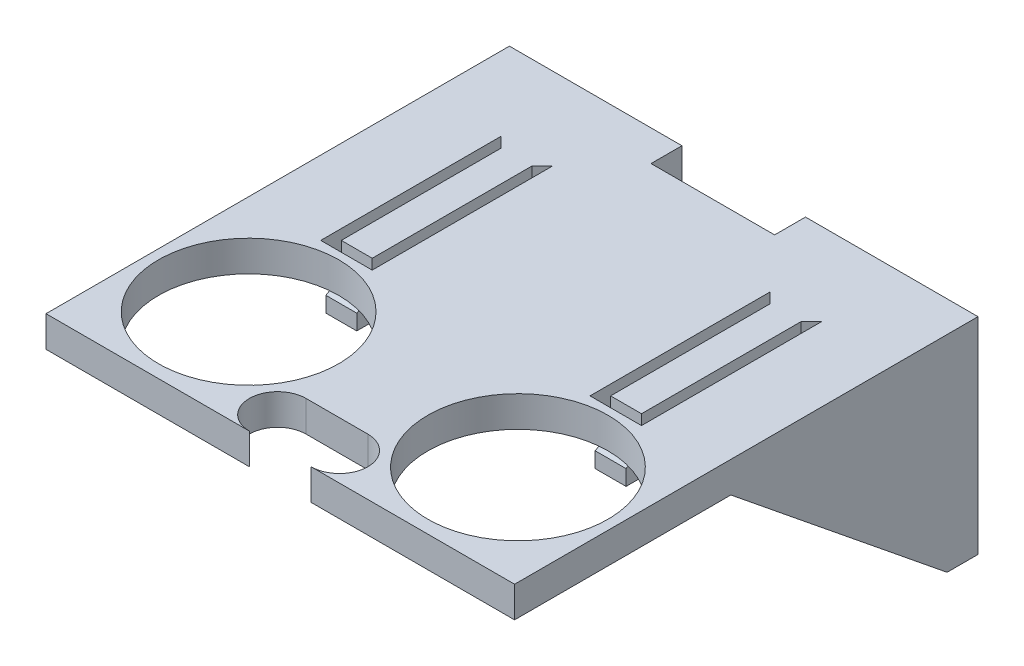
SolidWorks part; units mm, degrees
ref_plane "Front" through (0, 0, 0) normal (0, 0, 1) x (1, 0, 0)
ref_plane "Top" through (0, 0, 0) normal (0, 1, 0) x (1, 0, 0)
ref_plane "Right" through (0, 0, 0) normal (1, 0, 0) x (0, 0, -1)
sketch "Sketch1" plane through (0, 0, 0) normal (0, 0, 1) x (1, 0, 0)
  line L0 (-19.8496, -3.9653) -> (-19.8496, 16.0347)
  line L1 (-36.5996, 16.0347) -> (8.9004, 16.0347)
  line L2 (-36.5996, 16.0347) -> (-36.5996, -3.9653)
  line L3 (-36.5996, -3.9653) -> (8.9004, -3.9653)
  line L4 (8.9004, 16.0347) -> (8.9004, -3.9653)
  line L5 (-7.8496, -3.9653) -> (-7.8496, 16.0347)
  point P12 (-13.8496, 16.0347)
  dimension "D1" = 45.5
  dimension "D2" = 20
  dimension "D9" = 6
  dimension "D10" = 6
extrude "Boss-Extrude1" add sketch "Sketch1" along normal blind 3 contours L2 L3 L0 L1 | L5 L3 L4 L1 region at (-28.2246, 6.0347, 0) region at (0.5254, 6.0347, 0)
sketch "Sketch2" plane through (0, 0, 3) normal (0, 0, 1) x (1, 0, 0)
  line L1 (-36.5996, 16.0347) -> (8.9004, 16.0347)
  line L2 (-36.5996, 16.0347) -> (-36.5996, 13.0347)
  line L3 (-36.5996, 13.0347) -> (8.9004, 13.0347)
  line L4 (8.9004, 16.0347) -> (8.9004, 13.0347)
  line L5 (8.9004, 16.0347) -> (8.9004, -3.9653) construction
  dimension "D1" = 3
extrude "Boss-Extrude2" add sketch "Sketch2" along normal blind 42 contours L3 L4 L1 L2
sketch "Sketch3" plane through (0, 13.0347, 0) normal (0, -1, 0) x (-1, 0, 0)
  line L0 (36.5996, -45) -> (-8.9004, -45) construction
  line L1 (18.1746, -35) -> (9.5246, -35)
  circle A0 centre (26.9246, -35) radius 8.75
  circle A1 centre (0.7746, -35) radius 8.75
  point P8 (13.8496, -35)
  point P9 (13.8496, -45)
  dimension "D1" = 17.5
  dimension "D2" = 17.5
  dimension "D3" = 10
  dimension "D4" = 10
  dimension "D5" = 26.15
extrude "Cut-Extrude1" cut sketch "Sketch3" against normal through all contours A0 | A1 region at (-0.7746, 13.0347, 35) region at (-26.9246, 13.0347, 35)
sketch "Sketch4" plane through (8.9004, 0, 0) normal (1, 0, 0) x (0, 0, -1)
  line L0 (-3, -3.9653) -> (-24, 13.0347)
  line L1 (-45, 13.0347) -> (-3, 13.0347) construction
  line L2 (-24, 13.0347) -> (-3, 13.0347)
  line L3 (-3, 16.0347) -> (-3, -3.9653) construction
  line L4 (-3, 13.0347) -> (-3, -3.9653)
  dimension "D1" = 21
extrude "Boss-Extrude3" add sketch "Sketch4" against normal blind 2
pattern_linear "LPattern1" count 2 spacing 43.5 along (-1, 0, 0) of "Boss-Extrude3"
sketch "Sketch5" plane through (0, 13.0347, 0) normal (0, -1, 0) x (-1, 0, 0)
  line L0 (29.4246, -8) -> (29.4246, -25.5)
  line L1 (29.4246, -25.5) -> (24.4246, -25.5)
  line L2 (24.4246, -25.5) -> (24.4246, -8)
  line L3 (24.4246, -8) -> (25.4246, -8)
  line L4 (25.4246, -8) -> (25.4246, -24.5)
  line L5 (25.4246, -24.5) -> (28.4246, -24.5)
  line L6 (28.4246, -24.5) -> (28.4246, -8)
  line L7 (28.4246, -8) -> (29.4246, -8)
  line L8 (36.5996, -45) -> (-8.9004, -45) construction
  line L9 (34.5996, -3) -> (19.8496, -3) construction
  line L11 (13.8496, -45) -> (13.8496, -32.1492)
  line L12 (-0.7254, -8) -> (-1.7254, -8)
  line L13 (-0.7254, -24.5) -> (-0.7254, -8)
  line L14 (2.2746, -24.5) -> (-0.7254, -24.5)
  line L15 (2.2746, -8) -> (2.2746, -24.5)
  line L16 (3.2746, -8) -> (2.2746, -8)
  line L17 (3.2746, -25.5) -> (3.2746, -8)
  line L18 (-1.7254, -25.5) -> (3.2746, -25.5)
  line L19 (-1.7254, -8) -> (-1.7254, -25.5)
  point P2 (26.9246, -25.5)
  point P9 (0.7746, -35)
  point P11 (26.9246, -35)
  point P17 (13.8496, -45)
  point P28 (0.7746, -25.5)
  dimension "D1" = 1
  dimension "D2" = 1
  dimension "D3" = 3
  dimension "D4" = 1
  dimension "D5" = 19.5
  dimension "D6" = 5
extrude "Cut-Extrude2" cut sketch "Sketch5" against normal through all contours L0 L1 L2 L3 L4 L5 L6 L7 | L17 L16 L15 L14 L13 L12 L19 L18
sketch "Sketch6" plane through (-25.4246, 0, 0) normal (1, 0, 0) x (0, 0, -1)
  line L1 (-24.5, 13.0347) -> (-26, 12.1687)
  line L2 (-26, 12.1687) -> (-26, 10.6687)
  line L3 (-26, 10.6687) -> (-21.5, 10.6687)
  line L4 (-21.5, 10.6687) -> (-19.134, 13.0347)
  line L5 (-8, 13.0347) -> (-24.5, 13.0347) construction
  line L6 (-19.134, 13.0347) -> (-24.5, 13.0347)
  dimension "D1" = 45
  dimension "D2" = 3
  dimension "D3" = 1.5
  dimension "D4" = 60
  dimension "D5" = 1.5
extrude "Boss-Extrude4" add sketch "Sketch6" against normal blind 3
sketch "Sketch8" plane through (0, 13.0347, 0) normal (0, -1, 0) x (-1, 0, 0)
  line L0 (25.4246, -8) -> (2.2746, -8)
  point P4 (13.8496, -8)
  dimension "D1" = 23.15
ref_plane "Plane5" through (-13.8496, 13.0347, 8) normal (1, 0, 0) x (0, 0, -1)
mirror "Mirror7" about plane through (-13.8496, 13.0347, 8) normal (1, 0, 0) of "Boss-Extrude4"
sketch "Sketch9" plane through (0, 13.0347, 0) normal (0, -1, 0) x (-1, 0, 0)
  line L0 (16.8496, -45) -> (10.8496, -45)
  line L1 (16.8496, -39.5) -> (10.8496, -39.5)
  line L2 (36.5996, -45) -> (-8.9004, -45) construction
  arc A0 (16.8496, -45) -> (16.8496, -39.5) centre (16.8496, -42.25) ccw
  arc A1 (10.8496, -45) -> (10.8496, -39.5) centre (10.8496, -42.25) cw
  point P8 (13.8496, -45)
  point P9 (13.8496, -45)
  dimension "D2" = 6
  dimension "D1" = 5.5
extrude "Cut-Extrude3" cut sketch "Sketch9" against normal through all
sketch "Sketch10" plane through (0, 13.0347, 0) normal (0, -1, 0) x (-1, 0, 0)
  line L0 (10.8496, -39.5) -> (16.8496, -39.5) construction
  line L1 (8.8496, -27.5) -> (18.8496, -27.5)
  line L2 (8.8496, -27.5) -> (8.8496, -25)
  line L3 (8.8496, -25) -> (18.8496, -25)
  line L4 (18.8496, -27.5) -> (18.8496, -25)
  line L5 (36.5996, -45) -> (16.8496, -45) construction
  point P4 (13.8496, -27.5)
  point P9 (13.8496, -39.5)
  dimension "D1" = 10
  dimension "D2" = 2.5
  dimension "D3" = 20
extrude "Cut-Extrude4" cut sketch "Sketch10" against normal blind 2 contours L1 L4 L3 L2
sketch "Sketch11" plane through (-34.5996, 0, 0) normal (1, 0, 0) x (0, 0, -1)
  line L0 (-3, -3.9653) -> (-3, -0.4653)
  line L3 (-3, -3.9653) -> (-3, 13.0347) construction
  line L4 (-3, -0.4653) -> (-4.5, -0.4653)
  line L5 (-4.5, -0.4653) -> (-5.6178, -1.8461)
  line L6 (-24, 13.0347) -> (-3, -3.9653) construction
  line L7 (-5.6178, -1.8461) -> (-3, -3.9653)
  line L8 (-4.5, -0.4653) -> (-3, 1.3877)
  line L9 (-3, 1.3877) -> (-3, -0.4653)
  line M1 (-3, -3.9653) -> (-3, 13.0347)
  line M3 (-24, 13.0347) -> (-3, -3.9653)
  dimension "D1" = 1.5
  dimension "D2" = 3.5
extrude "Boss-Extrude5" add sketch "Sketch11" along normal up to surface (41.5 mm away) contours L4 L5 M3 M1 region at (-34.5996, -1.8771, 3.9648) up to face at (6.9004, 7.3681, 10)
sketch "Sketch13" plane through (0, 13.0347, 0) normal (0, -1, 0) x (-1, 0, 0)
  line L1 (28.4246, -19.134) -> (25.4246, -19.134)
  line L2 (28.4246, -19.134) -> (28.4246, -8)
  line L3 (28.4246, -8) -> (25.4246, -8)
  line L4 (25.4246, -19.134) -> (25.4246, -8)
  line L5 (2.2746, -19.134) -> (-0.7254, -19.134)
  line L6 (2.2746, -19.134) -> (2.2746, -8)
  line L7 (2.2746, -8) -> (-0.7254, -8)
  line L8 (-0.7254, -19.134) -> (-0.7254, -8)
extrude "Cut-Extrude6" cut sketch "Sketch13" against normal blind 1
chamfer "Chamfer1" distance 1 angle 45 2 edges at (-26.9246, 14.0347, 8) (-0.7746, 14.0347, 8)
extrude "Boss-Extrude6" add sketch "Sketch11<3>" along normal offset from surface (13.25 mm away) 7.5 contours L8 L4 M1 region at (-34.5996, 0.1524, 3.5) up to plane "Plane5"
sketch "Sketch11<3>" plane through (-34.5996, 0, 0) normal (1, 0, 0) x (0, 0, -1) same geometry as "Sketch11"
mirror "Mirror8" about plane through (-13.8496, 13.0347, 8) normal (1, 0, 0) of "Boss-Extrude6"
chamfer "Chamfer2" distance 1 angle 45 4 edges at (-28.4246, 14.5347, 8) (-25.4246, 14.5347, 8) (-2.2746, 14.5347, 8) (0.7254, 14.5347, 8)
sketch "Esquisse1" plane through (0, 0, 3) normal (0, 0, 1) x (1, 0, 0)
  line L0 (-13.8496, -0.4653) -> (-13.8496, 13.0347) construction
  line L1 (-13.8496, 6.2847) -> (-3.8496, 6.2847) construction
  line L3 (-6.3496, -0.4653) -> (-21.3496, -0.4653) construction
  line L4 (-13.8496, 6.2847) -> (-23.8496, 6.2847) construction
  circle A0 centre (-3.8496, 6.2847) radius 2.3
  circle A1 centre (-23.8496, 6.2847) radius 2.3
extrude "Enlèv. mat.-Extru.1" cut sketch "Esquisse1" against normal up to next
sketch "Esquisse2" plane through (0, 16.0347, 0) normal (0, 1, 0) x (1, 0, 0)
  line L0 (8.9004, 0) -> (-36.5996, 0) construction
  line L1 (-36.5996, 0) -> (-36.5996, -45) construction
  line L2 (-36.5996, -45) -> (8.9004, -45) construction
  line L3 (8.9004, -45) -> (8.9004, 0) construction
  line L4 (-35.6746, -35) -> (-18.1746, -35) construction
  line L5 (7.9754, -35) -> (-9.5246, -35) construction
  line L6 (-0.7746, -35) -> (-26.9246, -35) construction
  line L7 (-13.8496, -35) -> (-13.8496, -39.5) construction
  line L8 (-10.8496, -39.5) -> (-16.8496, -39.5) construction
  line L9 (-13.8496, -39.5) -> (-13.8496, -45) construction
  line L10 (-13.8496, -42.25) -> (-19.5996, -42.25) construction
  circle A0 centre (-26.9246, -35) radius 8.75 construction
  circle A1 centre (-0.7746, -35) radius 8.75 construction
  arc A2 (-16.8496, -39.5) -> (-16.8496, -45) centre (-16.8496, -42.25) ccw construction
  dimension "D1" = 26.15
  dimension "D2" = 17.5
  dimension "D3" = 5.5
  dimension "D4" = 5.75
  dimension "D5" = 4.5
sketch "Esquisse3" plane through (0, 13.0347, 0) normal (0, -1, 0) x (1, 0, 0)
  line L0 (-13.8496, 35) -> (-13.8496, 27.5) construction
  line L1 (-8.8496, 27.5) -> (-18.8496, 27.5) construction
  line L2 (-13.8496, 27.5) -> (-13.8496, 25) construction
  line L3 (-8.8496, 25) -> (-18.8496, 25) construction
  dimension "D1" = 7.5
  dimension "D2" = 2.5
